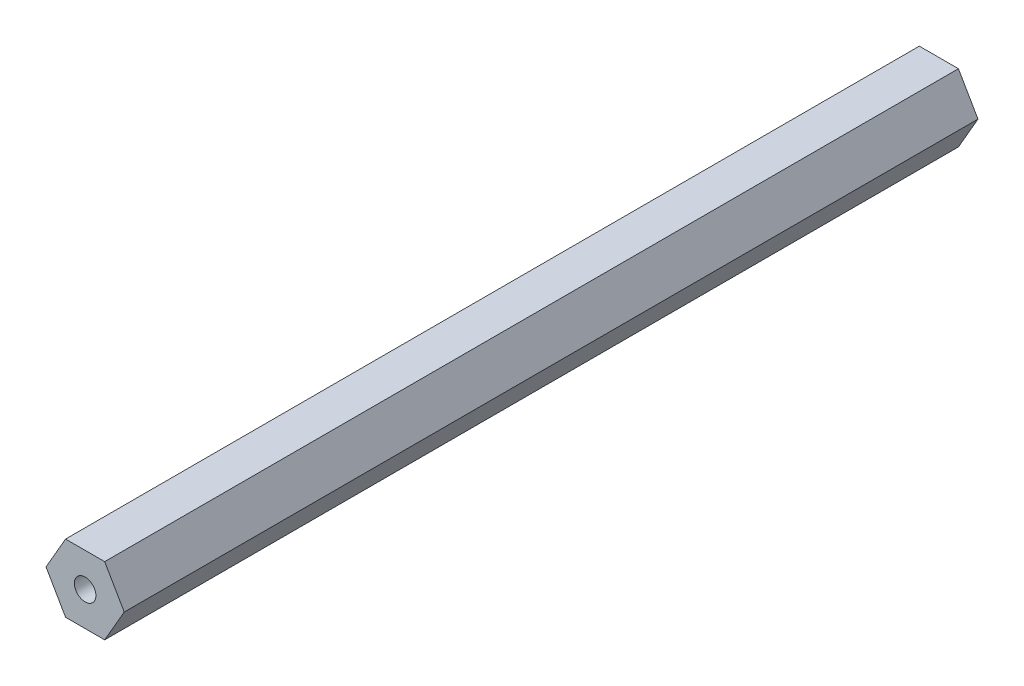
SolidWorks part; units mm, degrees
material "6061-T6 (SS)"
ref_plane "Front" through (0, 0, 0) normal (0, 0, 1) x (1, 0, 0)
ref_plane "Top" through (0, 0, 0) normal (0, 1, 0) x (1, 0, 0)
ref_plane "Right" through (0, 0, 0) normal (1, 0, 0) x (0, 0, -1)
sketch "Sketch1" plane through (0, 0, 0) normal (0, 0, 1) x (1, 0, 0)
  line L1 (7.3323, 0) -> (3.6662, 6.35)
  line L2 (3.6662, 6.35) -> (-3.6662, 6.35)
  line L3 (-3.6662, 6.35) -> (-7.3323, 0)
  line L4 (-7.3323, 0) -> (-3.6662, -6.35)
  line L5 (-3.6662, -6.35) -> (3.6662, -6.35)
  line L6 (3.6662, -6.35) -> (7.3323, 0)
  circle A0 centre (0, 0) radius 6.35 construction
  dimension "D1" = 12.7
extrude "Boss-Extrude1" add sketch "Sketch1" along normal blind 160.02
hole_wizard "#10-32 Tapped Hole1" positions "Sketch2" profile "Sketch4" tap size "#10-32" standard "ANSI Inch"
sketch "Sketch2" plane through (0, 0, 160.02) normal (0, 0, 1) x (1, 0, 0)
  point P0 (0, 0)
sketch "Sketch4" plane through (0, 0, 160.02) normal (1, 0, 0) x (0, -1, 0)
  line L0 (0, 0) -> (0, 77.4133)
  line L1 (0, 77.4133) -> (2.0193, 76.2)
  line L2 (2.0193, 76.2) -> (2.0193, 0)
  line L5 (2.0193, 0) -> (0, 0)
  line L10 (0, 77.4133) -> (-2.0193, 76.2) construction
  line L11 (0, -6.35) -> (0, 107.95) construction
  dimension "Tap Drill Dia." = 4.0386
  dimension "Tap Drill Depth" = 76.2
  dimension "Drill Angle" = 118
cosmetic thread "Hole Thread1" parameters "D1"=9.652, "D2"=4.826
